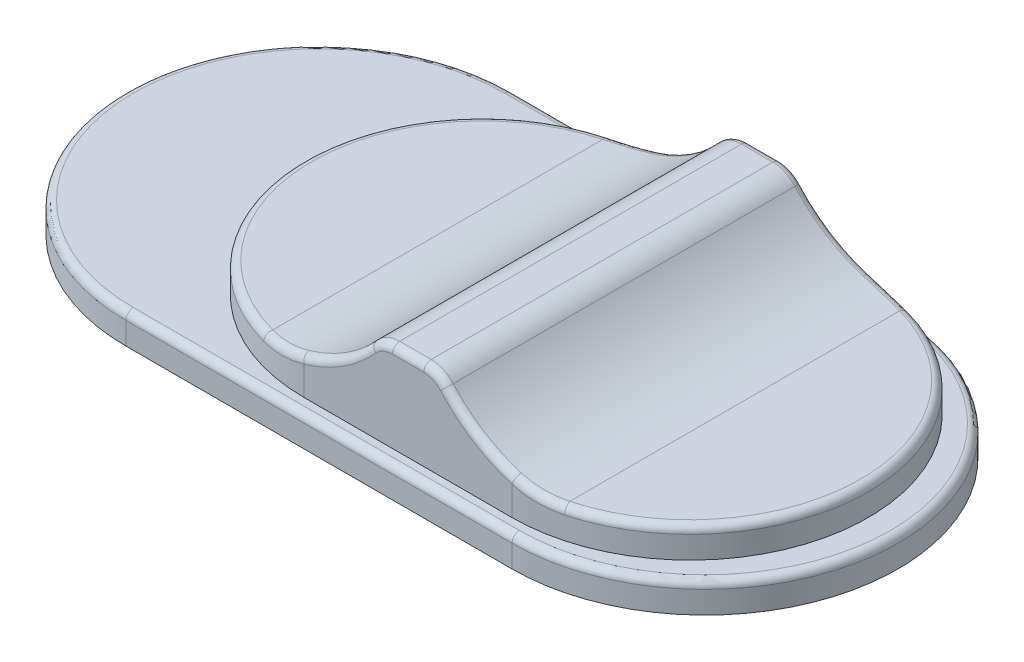
SolidWorks part; units mm, degrees
ref_plane "Front Plane" through (0, 0, 0) normal (0, 0, 1) x (1, 0, 0)
ref_plane "Top Plane" through (0, 0, 0) normal (0, 1, 0) x (1, 0, 0)
ref_plane "Right Plane" through (0, 0, 0) normal (1, 0, 0) x (0, 0, -1)
sketch "Sketch1" plane through (0, 0, 0) normal (0, 1, 0) x (1, 0, 0)
  line L0 (-6.5, 0) -> (6.5, 0) construction
  line L1 (-6.5, 6.5) -> (6.5, 6.5)
  line L2 (-6.5, -6.5) -> (6.5, -6.5)
  arc A0 (-6.5, 6.5) -> (-6.5, -6.5) centre (-6.5, 0) ccw
  arc A1 (6.5, -6.5) -> (6.5, 6.5) centre (6.5, 0) ccw
  point P3 (0, 0)
  dimension "D1" = 13
  dimension "D2" = 13
extrude "Boss-Extrude1" add sketch "Sketch1" along normal blind 1
sketch "Sketch2" plane through (0, 0, 0) normal (0, 0, 1) x (1, 0, 0)
  line L0 (-7, 1) -> (-7, 2)
  line L1 (-6.5, 1) -> (-13, 1) construction
  line L2 (-7, 2) -> (1.5, 2)
  line L3 (1.5, 2) -> (1.5, 4)
  line L4 (1.5, 4) -> (3.5, 4)
  line L5 (3.5, 4) -> (3.5, 2)
  line L6 (3.5, 2) -> (12, 2)
  line L7 (12, 2) -> (12, 1)
  line L8 (13, 0) -> (13, 1) construction
  line L9 (-7, 1) -> (12, 1)
  dimension "D1" = 2
  dimension "D2" = 8.5
  dimension "D3" = 1
  dimension "D4" = 2
  dimension "D5" = 1
extrude "Boss-Extrude2" add sketch "Sketch2" along normal offset from surface 0.5 and the other way offset from surface 0.5 up to face at (0, 0.5, 6.5) other way up to face at (0, 0.5, -6.5)
sketch "Sketch3" plane through (0, 2, 0) normal (0, 1, 0) x (1, 0, 0)
  line L0 (-1, 6) -> (-7, 6)
  line L1 (-7, 6) -> (-7, -6)
  line L2 (-7, -6) -> (-1, -6)
  line L3 (6, 6) -> (12, 6)
  line L4 (12, 6) -> (12, -6)
  line L5 (9, 6) -> (-7, 6) construction
  line L6 (9, -6) -> (-7, -6) construction
  line L7 (3.5, 6) -> (12, 6) construction
  line L8 (3.5, -6) -> (12, -6) construction
  line L9 (12, -3.4641) -> (12, 3.4641) construction
  line L10 (-7, -6) -> (-7, 6) construction
  line L11 (12, -6) -> (6, -6)
  arc A0 (-1, 6) -> (-1, -6) centre (-1, 0) ccw
  arc A1 (6, 6) -> (6, -6) centre (6, 0) cw
  line M1 (-7, 6) -> (-7, -6)
  line M2 (-7, -6) -> (1.5, -6)
  line M4 (1.5, 6) -> (-7, 6)
extrude "Cut-Extrude1" cut sketch "Sketch3" against normal up to surface (1 mm away) contours A0 M4 M1 | A0 L1 M2 | L4 A1 L11 | L3 A1 L4 region at (-5.6598, 2, -4.6598) region at (-5.6598, 2, 4.6598) region at (10.6598, 2, 4.6598) region at (10.6598, 2, -4.6598) up to face at (-0.3063, 1, 0)
fillet "Fillet1" radius 5 2 edges at (3.5, 2, 0) (1.5, 2, 0)
fillet "Fillet2" radius 1 2 edges at (3.5, 4, 0) (1.5, 4, 0)
fillet "Fillet3" radius 0.25 20 edges at (0.2103, 2.7983, -6) (1.5639, 3.9129, -6) (2.5, 4, -6) (3.4361, 3.9129, -6) (4.7897, 2.7983, -6) (4.7897, 2.7983, 6) (3.4361, 3.9129, 6) (2.5, 4, 6) (1.5639, 3.9129, 6) (0.2103, 2.7983, 6) (0, 1, -6.5) (13, 1, 0) (0, 1, 6.5) (12, 2, 0) (-13, 1, 0) (-7, 2, 0)
